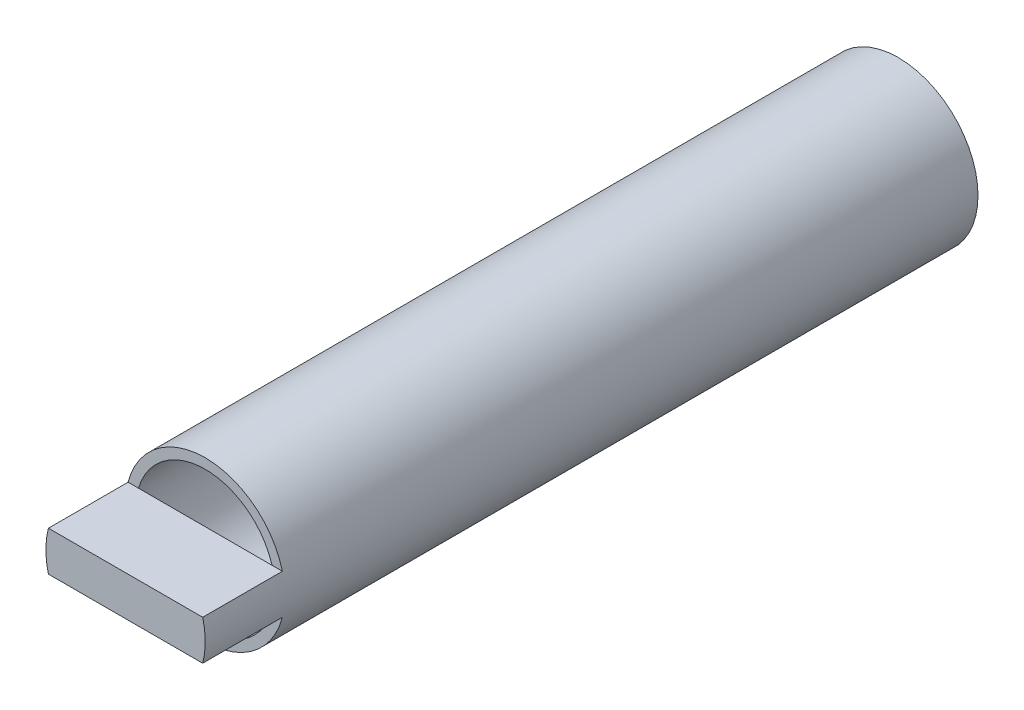
SolidWorks part; units mm, degrees
ref_plane "Front Plane" through (0, 0, 0) normal (0, 0, 1) x (1, 0, 0)
ref_plane "Top Plane" through (0, 0, 0) normal (0, 1, 0) x (1, 0, 0)
ref_plane "Right Plane" through (0, 0, 0) normal (1, 0, 0) x (0, 0, -1)
sketch "Sketch1" plane through (0, 0, 0) normal (0, 0, 1) x (1, 0, 0)
  circle A0 centre (0, 0) radius 10
  circle A1 centre (0, 0) radius 8.75
  dimension "D1" = 20
  dimension "D2" = 17.5
extrude "Boss-Extrude1" add sketch "Sketch1" along normal mid plane 87
sketch "Sketch2" plane through (0, 0, 43.5) normal (0, 0, 1) x (1, 0, 0)
  line L1 (9.6825, -2.5) -> (-9.6825, -2.5)
  line L3 (9.6825, 2.5) -> (-9.6825, 2.5)
  line L5 (9.6825, -2.5) -> (-9.6825, 2.5) construction
  line L6 (9.6825, 2.5) -> (-9.6825, -2.5) construction
  arc A0 (-9.6825, 2.5) -> (-9.6825, -2.5) centre (0, 0) ccw
  arc A1 (9.6825, -2.5) -> (9.6825, 2.5) centre (0, 0) ccw
  dimension "D1" = 20
  dimension "D2" = 5
extrude "Boss-Extrude2" add sketch "Sketch2" along normal blind 10
